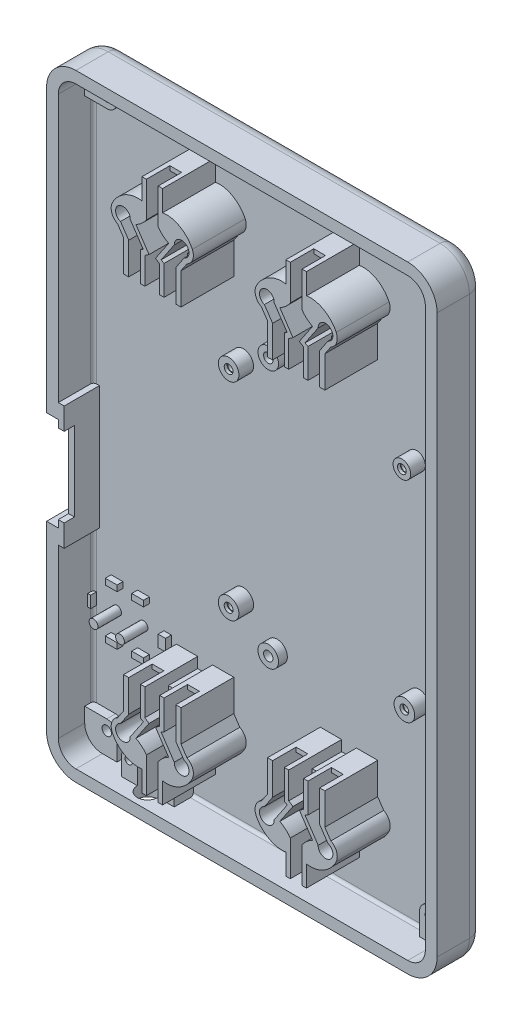
SolidWorks part; units mm, degrees
ref_plane "Alzado" through (0, 0, 0) normal (0, 0, 1) x (1, 0, 0)
ref_plane "Planta" through (0, 0, 0) normal (0, 1, 0) x (1, 0, 0)
ref_plane "Vista lateral" through (0, 0, 0) normal (1, 0, 0) x (0, 0, -1)
sketch "Croquis1" plane through (0, 0, 0) normal (0, 0, 1) x (1, 0, 0)
  line L1 (-97.3166, 96.9231) -> (15.6834, 96.9231)
  line L2 (-107.3166, 86.9231) -> (-107.3166, -103.0769)
  line L3 (-97.3166, -113.0769) -> (15.6834, -113.0769)
  line L4 (25.6834, 86.9231) -> (25.6834, -103.0769)
  arc A0 (15.6834, 96.9231) -> (25.6834, 86.9231) centre (15.6834, 86.9231) cw
  arc A1 (-97.3166, 96.9231) -> (-107.3166, 86.9231) centre (-97.3166, 86.9231) ccw
  arc A2 (15.6834, -113.0769) -> (25.6834, -103.0769) centre (15.6834, -103.0769) ccw
  arc A3 (-107.3166, -103.0769) -> (-97.3166, -113.0769) centre (-97.3166, -103.0769) ccw
  point P6 (25.6834, 96.9231)
  point P9 (-107.3166, 96.9231)
  point P14 (-107.3166, -113.0769)
  dimension "D3" = 10
  dimension "D1" = 210
  dimension "D2" = 133
extrude "Saliente-Extruir1" add sketch "Croquis1" along normal blind 16
fillet "Redondeo1" radius 5 8 edges at (-40.8166, 96.9231, 0) (22.7544, 93.9941, 0) (25.6834, -8.0769, 0) (22.7544, -110.148, 0) (-40.8166, -113.0769, 0) (-104.3877, -110.148, 0) (-107.3166, -8.0769, 0) (-104.3877, 93.9941, 0)
shell "Vaciado1" thickness 4 removed face at (-40.8166, -8.0769, 16)
sketch "Croquis4" plane through (0, 0, 0) normal (0, 0, 1) x (1, 0, 0)
  line L11 (-95.8166, 81.9231) -> (-103.3166, 81.9231)
  line L12 (-97.3166, -109.0769) -> (15.6834, -109.0769) construction
  line L17 (-103.3166, 86.9231) -> (-103.3166, -103.0769) construction
  line L19 (-85.549, -109.0769) -> (-78.3884, -109.0769)
  line L23 (-92.3166, 85.4231) -> (-92.3166, 92.9231)
  line L40 (15.6834, 92.9231) -> (-97.3166, 92.9231) construction
  line L42 (-85.549, -109.0769) -> (-85.549, -113.0769)
  line L43 (-107.3166, -8.0769) -> (25.6834, -8.0769)
  line L44 (-85.549, -113.0769) -> (-78.3884, -113.0769)
  line L45 (-78.3884, -109.0769) -> (-78.3884, -113.0769)
  line L47 (14.1834, 81.9231) -> (21.6834, 81.9231)
  line L48 (25.6834, -113.0769) -> (-107.3166, -113.0769)
  line L50 (25.6834, -113.0769) -> (25.6834, 96.9231)
  line L51 (25.6834, 96.9231) -> (-107.3166, 96.9231)
  line L52 (-107.3166, -113.0769) -> (-107.3166, 96.9231)
  line L53 (10.6834, 85.4231) -> (10.6834, 92.9231)
  line L54 (-92.3166, -101.5769) -> (-92.3166, -109.0769)
  line L55 (-95.8166, -98.0769) -> (-103.3166, -98.0769)
  line L56 (10.6834, -101.5769) -> (10.6834, -109.0769)
  line L57 (14.1834, -98.0769) -> (21.6834, -98.0769)
  circle A6 centre (-95.8166, 85.4231) radius 3.5
  circle A12 centre (-95.8166, 85.4231) radius 1.6
  circle A13 centre (-40.8166, -52.0552) radius 1.6
  circle A14 centre (14.1834, 85.4231) radius 1.6
  circle A15 centre (14.1834, 85.4231) radius 3.5
  circle A16 centre (-40.8166, 35.9013) radius 1.6
  circle A17 centre (-95.8166, -101.5769) radius 1.6
  circle A18 centre (-95.8166, -101.5769) radius 3.5
  circle A19 centre (14.1834, -101.5769) radius 1.6
  circle A20 centre (14.1834, -101.5769) radius 3.5
  arc A21 (-103.3166, 81.9231) -> (-92.3166, 92.9231) centre (-95.8166, 85.4231) cw
  arc A22 (10.6834, 92.9231) -> (21.6834, 81.9231) centre (14.1834, 85.4231) cw
  arc A23 (21.6834, -98.0769) -> (10.6834, -109.0769) centre (14.1834, -101.5769) cw
  arc A24 (-103.3166, -98.0769) -> (-92.3166, -109.0769) centre (-95.8166, -101.5769) ccw
  circle A25 centre (-40.8166, -52.0552) radius 3.5
  circle A26 centre (-40.8166, 35.9013) radius 3.5
extrude "Cortar-Extruir5" cut sketch "Croquis4" along normal through all both and the other way through all from surface contours A17 | A19 | A14 | A12 region at (-95.8166, 85.4231, 0) region at (14.1834, 85.4231, 0) region at (-95.8166, -101.5769, 0) region at (14.1834, -101.5769, 0) starting at face at (-40.8166, -8.0769, 4)
extrude "Cortar-Extruir6" cut sketch "Croquis4<19>" along normal blind 3 from surface contours A6 A12 | A15 A14 | A18 A17 | A20 A19 region at (-98.2215, 87.828, 0) region at (11.7785, 83.0182, 0) region at (-98.2215, -103.9818, 0) region at (11.7785, -99.172, 0) starting at face at (-97.4166, 85.4231, 0)
sketch "Croquis4<19>" plane through (0, 0, 0) normal (0, 0, 1) x (1, 0, 0) same geometry as "Croquis4"
extrude "Saliente-Extruir14" add sketch "Croquis4<21>" along normal blind 3 from surface contours L55 A24 L54 A18 | A18 A17 | A20 A19 | A23 L57 A20 L56 | A22 L53 A15 L47 | A21 L11 A6 L23 | A6 A12 | A15 A14 region at (-98.7646, 88.371, 0) region at (-98.2215, 87.828, 0) region at (17.1313, 88.371, 0) region at (11.7785, 83.0182, 0) region at (-98.2215, -103.9818, 0) region at (-98.7646, -104.5248, 0) region at (17.1313, -104.5248, 0) region at (11.7785, -99.172, 0) starting at face at (-97.4166, 85.4231, 4)
sketch "Croquis4<21>" plane through (0, 0, 0) normal (0, 0, 1) x (1, 0, 0) same geometry as "Croquis4"
extrude "Saliente-Extruir23" add sketch "Croquis4<27>" along normal blind 3 from surface contours A25 A13 | A26 A16 region at (-44.2176, -52.0552, 0) region at (-44.2176, 35.9013, 0) starting at face at (-40.8166, -8.0769, 4)
sketch "Croquis4<27>" plane through (0, 0, 0) normal (0, 0, 1) x (1, 0, 0) same geometry as "Croquis4"
extrude "Cortar-Extruir23" cut sketch "Croquis4<25>" along normal blind 3 from surface contours A26 A16 | A25 region at (-44.2176, 35.9013, 0) starting at face at (10.6834, 85.4231, 0)
sketch "Croquis4<25>" plane through (0, 0, 0) normal (0, 0, 1) x (1, 0, 0) same geometry as "Croquis4"
extrude "Cortar-Extruir22" cut sketch "Croquis4<24>" along normal blind 4 contours A16 | A16 | A13 | A13 region at (-40.8166, -52.0552, 0) region at (-40.8166, 35.9013, 0)
sketch "Croquis4<24>" plane through (0, 0, 0) normal (0, 0, 1) x (1, 0, 0) same geometry as "Croquis4"
sketch "Croquis5" plane through (0, 0, 0) normal (0, 0, 1) x (1, 0, 0)
  line L150 (-10.7322, 67.714) -> (-15.2148, 61.0683)
  line L241 (-107.3158, 96.9231) -> (-100.3166, 96.9231)
  line L242 (-107.3158, 96.9231) -> (-107.3158, 86.9231)
  line L253 (25.6842, -113.0769) -> (-107.3158, -113.0769)
  line L254 (25.6842, -113.0769) -> (25.6842, 96.9231)
  line L255 (25.6842, 96.9231) -> (-107.3158, 96.9231)
  line L257 (-107.3158, -113.0769) -> (-107.3158, 96.9231)
  line L269 (-21.5054, -83.2876) -> (-11.1236, -83.2876)
  line L290 (20.6834, 81.9231) -> (20.6834, -98.0769) construction
  line L298 (20.6834, 41.9231) -> (20.6834, 91.9231)
  line L319 (-6.5409, 51.0127) -> (-6.5409, 61.7386)
  line L321 (-20.3378, 51.0127) -> (-18.8378, 51.0127)
  line L323 (-24.3378, 52.515) -> (-20.3378, 52.515)
  line L325 (-13.7911, 56.1125) -> (-13.7911, 54.6136)
  line L327 (-19.3441, 61.5758) -> (-20.3378, 61.013)
  line L329 (-15.2148, 61.0683) -> (-13.7911, 60.108)
  line L331 (-18.3145, 81.3376) -> (-14.3145, 81.3376)
  line L333 (-12.2911, 61.013) -> (-12.2911, 51.0127)
  line L334 (-13.2849, 61.5758) -> (-12.2911, 61.013)
  line L448 (-22.0816, -81.7882) -> (-23.0929, -83.2876)
  line L529 (-20.3378, 51.0127) -> (-20.3378, 52.515)
  line L533 (-79.3166, -65.3411) -> (-76.8166, -65.3411)
  line L534 (-8.2911, -76.2618) -> (-8.2911, -74.757)
  line L536 (-105.3158, -41.0434) -> (-107.3716, -41.0434)
  line L537 (-24.3378, -67.1665) -> (-24.3378, -68.6689)
  line L538 (-21.8968, -83.8679) -> (-17.4141, -77.2221)
  line L540 (-24.3378, -77.98) -> (-24.3378, -67.1665)
  line L541 (-8.2911, -77.98) -> (-8.2911, -67.1665)
  line L542 (-26.088, -77.8924) -> (-28.1332, -80.9245)
  line L543 (-14.3145, -98.9873) -> (-14.3145, -97.4915)
  line L544 (-20.3378, -74.757) -> (-20.3378, -76.2618)
  line L545 (-20.3378, -77.1668) -> (-20.3378, -67.1665)
  line L546 (-12.8145, -98.9873) -> (-12.8145, -91.832)
  line L547 (-23.8176, -84.362) -> (-19.3441, -77.7297)
  line L548 (-18.8378, -72.2663) -> (-18.8378, -70.7675)
  line L551 (-8.2911, -67.1665) -> (-8.2911, -68.6689)
  line L552 (-8.2911, -77.98) -> (-5.4952, -82.1252)
  line L553 (-18.8378, -70.7675) -> (-13.7911, -70.7675)
  line L554 (-12.2911, -74.757) -> (-8.2911, -74.757)
  line L555 (-12.2911, -67.1665) -> (-8.2911, -67.1665)
  line L557 (-6.5409, -77.8924) -> (-4.4957, -80.9245)
  line L562 (20.6834, 81.9231) -> (20.6834, -98.0769) construction
  line L563 (-102.3166, -98.0769) -> (-102.3166, 81.9231) construction
  line L564 (-14.3145, -98.9873) -> (-14.3145, -86.9871)
  line L565 (-10.5473, -81.7882) -> (-5.7225, -81.7882)
  line L616 (-23.0929, -83.2876) -> (-28.5079, -83.2876)
  line L617 (-20.3378, -74.757) -> (-24.3378, -74.757)
  line L635 (-24.3378, -67.1665) -> (-26.088, -67.1665)
  line L650 (-18.3145, -86.9871) -> (-18.3145, -98.9873)
  line L652 (-12.2911, -67.1665) -> (-12.2911, -68.6689)
  line L653 (-24.3378, -67.1665) -> (-20.3378, -67.1665)
  line L661 (-18.3145, -98.9873) -> (-14.3145, -98.9873)
  line L662 (-18.3145, -98.9873) -> (-19.8145, -98.9873)
  line L665 (-13.7911, -76.2618) -> (-13.7911, -67.1665)
  line L666 (-9.536, -83.2876) -> (-4.121, -83.2876)
  line L667 (-12.2911, -68.6689) -> (-8.2911, -68.6689)
  line L668 (-18.3145, -98.9873) -> (-18.3145, -86.9871)
  line L669 (-20.494, -81.7882) -> (-12.1349, -81.7882)
  line L671 (-12.2911, -76.2618) -> (-8.2911, -76.2618)
  line L673 (-12.2911, -67.1665) -> (-13.7911, -67.1665)
  line L674 (-19.8145, -98.9873) -> (-19.8145, -91.832)
  line L675 (-24.3378, -74.757) -> (-24.3378, -76.2618)
  line L676 (-12.2911, -76.2618) -> (-12.2911, -74.757)
  line L677 (-17.4141, -77.2221) -> (-18.8378, -76.2618)
  line L679 (-79.3166, -65.3411) -> (-79.3166, -69.3411)
  line L681 (-26.9065, -81.7882) -> (-22.0816, -81.7882)
  line L682 (-8.2911, -67.1665) -> (-6.5409, -67.1665)
  line L683 (-24.3378, -77.98) -> (-27.1338, -82.1252)
  line L684 (-14.3145, -86.9871) -> (-14.3145, -98.9873)
  line L685 (-18.8378, -76.2618) -> (-18.8378, -67.1665)
  line L687 (-14.3145, -98.9873) -> (-12.8145, -98.9873)
  line L689 (-18.8378, -72.2663) -> (-13.7911, -72.2663)
  line L690 (-97.3166, -109.0769) -> (15.6834, -109.0769) construction
  line L691 (-81.878, -113.0769) -> (-74.9407, -113.0769)
  line L692 (-81.878, -113.0769) -> (-81.878, -109.0769)
  line L693 (-81.878, -109.0769) -> (-74.9407, -109.0769)
  line L694 (-74.9407, -113.0769) -> (-74.9407, -109.0769)
  line L695 (-87.3438, -109.0769) -> (-81.878, -109.0769)
  line L697 (-84.8438, -103.0769) -> (-71.844, -103.0769)
  line L698 (-87.3438, -103.0769) -> (-87.3438, -109.0769)
  line L699 (-84.8438, -100.5769) -> (-71.844, -100.5769)
  line L700 (-69.344, -103.0769) -> (-69.344, -109.0769)
  line L701 (-92.3166, -109.0769) -> (10.6834, -109.0769) construction
  line L702 (-74.9407, -109.0769) -> (-69.344, -109.0769)
  line L704 (-78.4093, -109.0769) -> (-78.4093, -113.0769)
  line L705 (-102.3166, -74.8411) -> (-79.3166, -74.8411)
  line L706 (-102.3166, -74.8411) -> (-102.3166, -59.8411)
  line L707 (-102.3166, -59.8411) -> (-79.3166, -59.8411)
  line L708 (-79.3166, -74.8411) -> (-79.3166, -59.8411)
  line L709 (-79.3166, -74.8411) -> (-84.3166, -74.8411)
  line L710 (-79.3166, -74.8411) -> (-79.3166, -59.8411)
  line L711 (-79.3166, -59.8411) -> (-84.3166, -59.8411)
  line L713 (-97.3166, -59.8411) -> (-93.3166, -59.8411)
  line L714 (-93.3166, -59.8411) -> (-88.3166, -59.8411)
  line L716 (-93.3166, -74.8411) -> (-88.3166, -74.8411)
  line L718 (-97.3166, -59.8411) -> (-97.3166, -74.8411)
  line L719 (-97.3166, -74.8411) -> (-93.3166, -74.8411)
  line L720 (-93.3166, -59.8411) -> (-93.3166, -74.8411)
  line L722 (-102.3166, -59.8411) -> (-97.3166, -59.8411)
  line L723 (-102.3166, -59.8411) -> (-102.3166, -74.8411)
  line L724 (-102.3166, -74.8411) -> (-97.3166, -74.8411)
  line L726 (-88.3166, -59.8411) -> (-84.3166, -59.8411)
  line L727 (-88.3166, -59.8411) -> (-88.3166, -74.8411)
  line L728 (-88.3166, -74.8411) -> (-84.3166, -74.8411)
  line L729 (-84.3166, -59.8411) -> (-84.3166, -74.8411)
  line L730 (-102.3166, -59.8411) -> (-79.3166, -59.8411)
  line L734 (-79.3166, -74.8411) -> (-102.3166, -74.8411)
  line L738 (-79.3166, -69.3411) -> (-76.8166, -69.3411)
  line L743 (-102.3166, -65.3411) -> (-102.3166, -69.3411)
  line L744 (-76.8166, -65.3411) -> (-76.8166, -69.3411)
  line L745 (-8.8113, -84.362) -> (-13.2849, -77.7297)
  line L746 (-26.088, -67.1665) -> (-26.088, -77.8924)
  line L751 (-79.3166, -69.3411) -> (-79.3166, -65.3411)
  line L754 (-79.3166, -65.3411) -> (-79.3166, -69.3411)
  line L757 (-97.3166, -74.8411) -> (-93.3166, -74.8411)
  line L758 (-97.3166, -74.8411) -> (-97.3166, -76.8411)
  line L759 (-97.3166, -76.8411) -> (-93.3166, -76.8411)
  line L760 (-93.3166, -74.8411) -> (-93.3166, -76.8411)
  line L761 (-88.3166, -74.8411) -> (-84.3166, -74.8411)
  line L762 (-88.3166, -74.8411) -> (-88.3166, -76.8411)
  line L763 (-88.3166, -76.8411) -> (-84.3166, -76.8411)
  line L764 (-84.3166, -74.8411) -> (-84.3166, -76.8411)
  line L765 (-97.3166, -59.8411) -> (-93.3166, -59.8411)
  line L766 (-97.3166, -59.8411) -> (-97.3166, -57.8411)
  line L767 (-97.3166, -57.8411) -> (-93.3166, -57.8411)
  line L768 (-93.3166, -59.8411) -> (-93.3166, -57.8411)
  line L769 (-88.3166, -59.8411) -> (-84.3166, -59.8411)
  line L770 (-88.3166, -59.8411) -> (-88.3166, -57.8411)
  line L771 (-88.3166, -57.8411) -> (-84.3166, -57.8411)
  line L772 (-84.3166, -59.8411) -> (-84.3166, -57.8411)
  line L776 (-103.3166, 81.9231) -> (-103.3166, -98.0769) construction
  line L777 (-107.3158, -41.0434) -> (-77.3158, -41.0434)
  line L778 (-107.3158, -41.0434) -> (-107.3158, -9.0434)
  line L779 (-107.3158, -9.0434) -> (-77.3158, -9.0434)
  line L780 (-77.3158, -41.0434) -> (-77.3158, -9.0434)
  line L781 (-77.3158, -41.0434) -> (-87.3158, -41.0434)
  line L782 (-77.3158, -41.0434) -> (-77.3158, -9.0434)
  line L783 (-77.3158, -9.0434) -> (-87.3158, -9.0434)
  line L784 (-87.3158, -41.0434) -> (-87.3158, -9.0434)
  line L785 (-107.3158, -9.0434) -> (-87.3158, -9.0434)
  line L786 (-107.3158, -9.0434) -> (-107.3158, -13.0467)
  line L787 (-107.3158, -13.0467) -> (-87.3158, -13.0467)
  line L788 (-87.3158, -9.0434) -> (-87.3158, -13.0467)
  line L789 (-87.3158, -13.0467) -> (-77.3158, -13.0467)
  line L790 (-87.3158, -13.0467) -> (-87.3158, -27.5467)
  line L791 (-87.3158, -27.5467) -> (-77.3158, -27.5467)
  line L792 (-77.3158, -13.0467) -> (-77.3158, -27.5467)
  line L793 (-87.3158, -41.0434) -> (-105.3158, -41.0434)
  line L794 (-87.3158, -41.0434) -> (-87.3158, -9.0434)
  line L795 (-87.3158, -9.0434) -> (-105.3158, -9.0434)
  line L796 (-105.3158, -41.0434) -> (-105.3158, -9.0434)
  line L797 (-105.3158, -9.0434) -> (-103.3166, -9.0434)
  line L798 (-105.3158, -9.0434) -> (-105.3158, -41.0434)
  line L799 (-105.3158, -41.0434) -> (-103.3166, -41.0434)
  line L800 (-103.3166, -9.0434) -> (-103.3166, -41.0434)
  line L801 (-105.3158, -41.0434) -> (-105.3158, -13.0467)
  line L802 (-103.3166, -9.0434) -> (-101.3158, -9.0434)
  line L803 (-103.3166, -9.0434) -> (-103.3166, -11.5434)
  line L804 (-103.3166, -11.5434) -> (-101.3158, -11.5434)
  line L805 (-101.3158, -9.0434) -> (-101.3158, -11.5434)
  line L806 (-103.3166, -41.0434) -> (-101.3158, -41.0434)
  line L807 (-103.3166, -41.0434) -> (-103.3166, -38.5434)
  line L808 (-103.3166, -38.5434) -> (-101.3158, -38.5434)
  line L809 (-101.3158, -41.0434) -> (-101.3158, -38.5434)
  line L810 (-101.3158, -9.0434) -> (-103.3166, -9.0434)
  line L811 (-101.3158, -9.0434) -> (-101.3158, -4.0434)
  line L812 (-101.3158, -4.0434) -> (-103.3166, -4.0434)
  line L813 (-103.3166, -9.0434) -> (-103.3166, -4.0434)
  line L814 (-101.3158, -41.0434) -> (-103.3166, -41.0434)
  line L815 (-101.3158, -41.0434) -> (-101.3158, -46.0434)
  line L816 (-101.3158, -46.0434) -> (-103.3166, -46.0434)
  line L817 (-103.3166, -41.0434) -> (-103.3166, -46.0434)
  line L818 (-101.3158, -11.5434) -> (-103.3166, -11.5434)
  line L819 (-101.3158, -11.5434) -> (-101.3158, -38.5434)
  line L820 (-101.3158, -38.5434) -> (-103.3166, -38.5434)
  line L821 (-103.3166, -11.5434) -> (-103.3166, -38.5434)
  line L822 (-56.3166, 31.4433) -> (10.6834, 31.4433)
  line L823 (-56.3166, 31.4433) -> (-56.3166, -46.5567)
  line L824 (-56.3166, -46.5567) -> (10.6834, -46.5567)
  line L825 (10.6834, 31.4433) -> (10.6834, -46.5567)
  line L826 (-20.3378, 60.108) -> (-24.3378, 60.108)
  line L827 (-18.3145, 82.8335) -> (-18.3145, 81.3376)
  line L828 (-56.3166, 31.4433) -> (-50.5567, 31.4433)
  line L829 (10.6834, 31.4433) -> (5.0745, 31.4433)
  line L830 (10.6834, 31.4433) -> (10.6834, 28.1628)
  line L833 (10.6834, -46.5567) -> (4.7834, -46.5567)
  line L834 (10.6834, -46.5567) -> (10.6834, -43.3567)
  line L837 (-56.3166, 31.4433) -> (-56.3166, 27.9366)
  line L840 (-56.3166, -46.5567) -> (-50.394, -46.5567)
  line L841 (-56.3166, -46.5567) -> (-56.3166, -42.7216)
  line L846 (-18.3145, -98.9873) -> (-18.3145, -97.4915)
  line L847 (-20.3378, -76.2618) -> (-24.3378, -76.2618)
  line L848 (-20.3378, -67.1665) -> (-20.3378, -68.6689)
  line L849 (-13.2849, -77.7297) -> (-12.2911, -77.1668)
  line L850 (-12.2911, -77.1668) -> (-12.2911, -67.1665)
  line L851 (-18.3145, -97.4915) -> (-14.3145, -97.4915)
  line L853 (-15.2148, -77.2221) -> (-13.7911, -76.2618)
  line L854 (-19.3441, -77.7297) -> (-20.3378, -77.1668)
  line L857 (-13.7911, -72.2663) -> (-13.7911, -70.7675)
  line L858 (-24.3378, -68.6689) -> (-20.3378, -68.6689)
  line L859 (-20.3378, -67.1665) -> (-18.8378, -67.1665)
  line L862 (-6.5409, -67.1665) -> (-6.5409, -77.8924)
  line L865 (-10.7322, -83.8679) -> (-15.2148, -77.2221)
  line L866 (-26.088, 51.0127) -> (-26.088, 61.7386)
  line L867 (-8.8113, 68.2081) -> (-13.2849, 61.5758)
  line L868 (-18.8378, 56.1125) -> (-13.7911, 56.1125)
  line L869 (-14.3145, 82.8335) -> (-12.8145, 82.8335)
  line L870 (-18.8378, 60.108) -> (-18.8378, 51.0127)
  line L871 (-14.3145, 70.8333) -> (-14.3145, 82.8335)
  line L873 (-24.3378, 61.8262) -> (-27.1338, 65.9714)
  line L874 (-8.2911, 51.0127) -> (-6.5409, 51.0127)
  line L876 (-26.9065, 65.6344) -> (-22.0816, 65.6344)
  line L877 (-17.4141, 61.0683) -> (-18.8378, 60.108)
  line L878 (-12.2911, 60.108) -> (-12.2911, 58.6032)
  line L881 (-24.3378, 58.6032) -> (-24.3378, 60.108)
  line L882 (-19.8145, 82.8335) -> (-19.8145, 75.6781)
  line L884 (-12.2911, 51.0127) -> (-13.7911, 51.0127)
  line L885 (-12.2911, 60.108) -> (-8.2911, 60.108)
  line L887 (-20.494, 65.6344) -> (-12.1349, 65.6344)
  line L888 (-18.3145, 82.8335) -> (-18.3145, 70.8333)
  line L889 (-12.2911, 52.515) -> (-8.2911, 52.515)
  line L891 (-9.536, 67.1338) -> (-4.121, 67.1338)
  line L892 (-13.7911, 60.108) -> (-13.7911, 51.0127)
  line L893 (-18.3145, 82.8335) -> (-19.8145, 82.8335)
  line L895 (-18.3145, 82.8335) -> (-14.3145, 82.8335)
  line L896 (-24.3378, 51.0127) -> (-20.3378, 51.0127)
  line L897 (-12.2911, 51.0127) -> (-12.2911, 52.515)
  line L899 (-18.3145, 70.8333) -> (-18.3145, 82.8335)
  line L900 (-24.3378, 51.0127) -> (-26.088, 51.0127)
  line L901 (-20.3378, 58.6032) -> (-24.3378, 58.6032)
  line L903 (-23.0929, 67.1338) -> (-28.5079, 67.1338)
  line L904 (-10.5473, 65.6344) -> (-5.7225, 65.6344)
  line L905 (-14.3145, 82.8335) -> (-14.3145, 70.8333)
  line L906 (-6.5409, 61.7386) -> (-4.4957, 64.7707)
  line L907 (-12.2911, 51.0127) -> (-8.2911, 51.0127)
  line L910 (-12.2911, 58.6032) -> (-8.2911, 58.6032)
  line L911 (-18.8378, 54.6136) -> (-13.7911, 54.6136)
  line L913 (-8.2911, 61.8262) -> (-5.4952, 65.9714)
  line L914 (-8.2911, 51.0127) -> (-8.2911, 52.515)
  line L916 (-18.8378, 56.1125) -> (-18.8378, 54.6136)
  line L917 (-23.8176, 68.2081) -> (-19.3441, 61.5758)
  line L918 (-12.8145, 82.8335) -> (-12.8145, 75.6781)
  line L919 (-20.3378, 61.013) -> (-20.3378, 51.0127)
  line L920 (-20.3378, 58.6032) -> (-20.3378, 60.108)
  line L921 (-14.3145, 82.8335) -> (-14.3145, 81.3376)
  line L923 (-26.088, 61.7386) -> (-28.1332, 64.7707)
  line L924 (-8.2911, 61.8262) -> (-8.2911, 51.0127)
  line L925 (-24.3378, 61.8262) -> (-24.3378, 51.0127)
  line L927 (-21.8968, 67.714) -> (-17.4141, 61.0683)
  line L928 (-24.3378, 51.0127) -> (-24.3378, 52.515)
  line L929 (-8.2911, 60.108) -> (-8.2911, 58.6032)
  line L930 (-22.0816, 65.6344) -> (-23.0929, 67.1338)
  line L934 (-21.5054, 67.1338) -> (-11.1236, 67.1338)
  line L937 (-105.3158, -13.0467) -> (-107.3716, -13.0467)
  line L938 (-60.1262, 67.1338) -> (-70.508, 67.1338)
  line L939 (-59.55, 65.6344) -> (-58.5386, 67.1338)
  line L941 (-73.3404, 60.108) -> (-73.3404, 58.6032)
  line L942 (-57.2938, 51.0127) -> (-57.2938, 52.515)
  line L943 (-59.7348, 67.714) -> (-64.2174, 61.0683)
  line L944 (-57.2938, 61.8262) -> (-57.2938, 51.0127)
  line L945 (-73.3404, 61.8262) -> (-73.3404, 51.0127)
  line L946 (-55.5435, 61.7386) -> (-53.4983, 64.7707)
  line L947 (-67.3171, 82.8335) -> (-67.3171, 81.3376)
  line L949 (-61.2938, 58.6032) -> (-61.2938, 60.108)
  line L950 (-61.2938, 61.013) -> (-61.2938, 51.0127)
  line L951 (-68.8171, 82.8335) -> (-68.8171, 75.6781)
  line L952 (-57.814, 68.2081) -> (-62.2875, 61.5758)
  line L953 (-62.7938, 56.1125) -> (-62.7938, 54.6136)
  line L955 (-73.3404, 51.0127) -> (-73.3404, 52.515)
  line L956 (-73.3404, 61.8262) -> (-76.1364, 65.9714)
  line L957 (-62.7938, 54.6136) -> (-67.8404, 54.6136)
  line L959 (-69.3404, 58.6032) -> (-73.3404, 58.6032)
  line L960 (-69.3404, 51.0127) -> (-73.3404, 51.0127)
  line L961 (-75.0906, 61.7386) -> (-77.1358, 64.7707)
  line L962 (-67.3171, 82.8335) -> (-67.3171, 70.8333)
  line L963 (-71.0842, 65.6344) -> (-75.9091, 65.6344)
  line L964 (-58.5386, 67.1338) -> (-53.1237, 67.1338)
  line L966 (-61.2938, 58.6032) -> (-57.2938, 58.6032)
  line L967 (-57.2938, 51.0127) -> (-55.5435, 51.0127)
  line L968 (-63.3171, 70.8333) -> (-63.3171, 82.8335)
  line L969 (-69.3404, 51.0127) -> (-69.3404, 52.515)
  line L970 (-62.7925, -72.2582) -> (-62.7925, -70.7594)
  line L971 (-67.8391, -70.7594) -> (-62.7925, -70.7594)
  line L972 (-67.8391, -72.2582) -> (-67.8391, -70.7594)
  line L973 (-67.8391, -72.2582) -> (-62.7925, -72.2582)
  line L974 (-63.3158, -98.9792) -> (-63.3158, -97.4834)
  line L975 (-67.3158, -97.4834) -> (-63.3158, -97.4834)
  line L976 (-67.3158, -98.9792) -> (-67.3158, -97.4834)
  line L977 (-67.3158, -98.9792) -> (-63.3158, -98.9792)
  line L978 (-59.5486, -81.7801) -> (-54.7238, -81.7801)
  line L979 (-69.4953, -81.7801) -> (-61.1362, -81.7801)
  line L980 (-58.5373, -83.2795) -> (-53.1224, -83.2795)
  line L981 (-70.5067, -83.2795) -> (-60.1249, -83.2795)
  line L982 (-72.0942, -83.2795) -> (-77.5092, -83.2795)
  line L983 (-71.0829, -81.7801) -> (-72.0942, -83.2795)
  line L984 (-73.3391, -74.7489) -> (-73.3391, -76.2537)
  line L985 (-69.3391, -76.2537) -> (-73.3391, -76.2537)
  line L986 (-69.3391, -74.7489) -> (-69.3391, -76.2537)
  line L987 (-69.3391, -74.7489) -> (-73.3391, -74.7489)
  line L988 (-57.2925, -76.2537) -> (-57.2925, -74.7489)
  line L989 (-61.2925, -74.7489) -> (-57.2925, -74.7489)
  line L990 (-61.2925, -76.2537) -> (-61.2925, -74.7489)
  line L991 (-61.2925, -76.2537) -> (-57.2925, -76.2537)
  line L992 (-57.2925, -67.1584) -> (-57.2925, -68.6608)
  line L993 (-61.2925, -68.6608) -> (-57.2925, -68.6608)
  line L994 (-61.2925, -67.1584) -> (-61.2925, -68.6608)
  line L995 (-61.2925, -67.1584) -> (-57.2925, -67.1584)
  line L996 (-69.3391, -67.1584) -> (-69.3391, -68.6608)
  line L997 (-73.3391, -68.6608) -> (-69.3391, -68.6608)
  line L998 (-73.3391, -67.1584) -> (-73.3391, -68.6608)
  line L999 (-73.3391, -67.1584) -> (-69.3391, -67.1584)
  line L1000 (-69.3391, -77.1587) -> (-69.3391, -67.1584)
  line L1001 (-67.3158, -98.9792) -> (-68.8158, -98.9792)
  line L1002 (-62.7925, -76.2537) -> (-62.7925, -67.1584)
  line L1003 (-57.2925, -67.1584) -> (-55.5422, -67.1584)
  line L1004 (-73.3391, -77.9719) -> (-76.1351, -82.1171)
  line L1005 (-62.2862, -77.7216) -> (-61.2925, -77.1587)
  line L1006 (-64.2161, -77.214) -> (-62.7925, -76.2537)
  line L1007 (-61.2925, -67.1584) -> (-62.7925, -67.1584)
  line L1008 (-73.3391, -77.9719) -> (-73.3391, -67.1584)
  line L1009 (-63.3158, -86.979) -> (-63.3158, -98.9792)
  line L1010 (-57.8126, -84.3539) -> (-62.2862, -77.7216)
  line L1011 (-69.3391, -67.1584) -> (-67.8391, -67.1584)
  line L1012 (-67.8391, -76.2537) -> (-67.8391, -67.1584)
  line L1013 (-57.2925, -77.9719) -> (-57.2925, -67.1584)
  line L1014 (-55.5422, -77.8843) -> (-53.497, -80.9164)
  line L1015 (-73.3391, -67.1584) -> (-75.0893, -67.1584)
  line L1016 (-55.5422, -67.1584) -> (-55.5422, -77.8843)
  line L1017 (-68.8158, -98.9792) -> (-68.8158, -91.8239)
  line L1018 (-66.4154, -77.214) -> (-67.8391, -76.2537)
  line L1019 (-68.3454, -77.7216) -> (-69.3391, -77.1587)
  line L1020 (-61.8158, -98.9792) -> (-61.8158, -91.8239)
  line L1021 (-67.3158, -98.9792) -> (-67.3158, -86.979)
  line L1022 (-75.0893, -67.1584) -> (-75.0893, -77.8843)
  line L1023 (-75.0893, -77.8843) -> (-77.1345, -80.9164)
  line L1024 (-57.2925, -77.9719) -> (-54.4965, -82.1171)
  line L1025 (-59.7335, -83.8597) -> (-64.2161, -77.214)
  line L1026 (-70.8981, -83.8597) -> (-66.4154, -77.214)
  line L1027 (-63.3158, -98.9792) -> (-63.3158, -86.979)
  line L1028 (-61.2925, -77.1587) -> (-61.2925, -67.1584)
  line L1029 (-63.3158, -98.9792) -> (-61.8158, -98.9792)
  line L1030 (-72.8189, -84.3539) -> (-68.3454, -77.7216)
  line L1031 (-67.3158, -86.979) -> (-67.3158, -98.9792)
  line L1032 (-75.9078, -81.7801) -> (-71.0829, -81.7801)
  line L1033 (-57.2938, 51.0127) -> (-61.2938, 51.0127)
  line L1034 (-102.3166, -69.3411) -> (-103.3166, -69.3411)
  line L1035 (-102.3166, -69.3411) -> (-102.3166, -65.3411)
  line L1036 (-102.3166, -65.3411) -> (-103.3166, -65.3411)
  line L1037 (-103.3166, -69.3411) -> (-103.3166, -65.3411)
  line L1038 (-63.3171, 82.8335) -> (-67.3171, 82.8335)
  line L1039 (-63.3171, 82.8335) -> (-61.8171, 82.8335)
  line L1040 (-67.8404, 60.108) -> (-67.8404, 51.0127)
  line L1041 (-72.0956, 67.1338) -> (-77.5105, 67.1338)
  line L1042 (-69.3404, 52.515) -> (-73.3404, 52.515)
  line L1043 (-63.3171, 82.8335) -> (-63.3171, 70.8333)
  line L1044 (-61.1375, 65.6344) -> (-69.4967, 65.6344)
  line L1045 (-69.3404, 60.108) -> (-73.3404, 60.108)
  line L1046 (-69.3404, 51.0127) -> (-67.8404, 51.0127)
  line L1047 (-61.8171, 82.8335) -> (-61.8171, 75.6781)
  line L1048 (-57.2938, 58.6032) -> (-57.2938, 60.108)
  line L1049 (-69.3404, 60.108) -> (-69.3404, 58.6032)
  line L1050 (-64.2174, 61.0683) -> (-62.7938, 60.108)
  line L1051 (-54.7251, 65.6344) -> (-59.55, 65.6344)
  line L1052 (-73.3404, 51.0127) -> (-75.0906, 51.0127)
  line L1053 (-57.2938, 61.8262) -> (-54.4978, 65.9714)
  line L1054 (-67.3171, 70.8333) -> (-67.3171, 82.8335)
  line L1055 (-62.7938, 60.108) -> (-62.7938, 51.0127)
  line L1056 (-67.3171, 82.8335) -> (-68.8171, 82.8335)
  line L1057 (-62.7938, 56.1125) -> (-67.8404, 56.1125)
  line L1058 (-72.8202, 68.2081) -> (-68.3467, 61.5758)
  line L1059 (-55.5435, 51.0127) -> (-55.5435, 61.7386)
  line L1060 (-63.3171, 82.8335) -> (-63.3171, 81.3376)
  line L1061 (-61.2938, 60.108) -> (-57.2938, 60.108)
  line L1062 (-61.2938, 51.0127) -> (-61.2938, 52.515)
  line L1063 (-68.3467, 61.5758) -> (-69.3404, 61.013)
  line L1064 (-69.3404, 61.013) -> (-69.3404, 51.0127)
  line L1065 (-63.3171, 81.3376) -> (-67.3171, 81.3376)
  line L1066 (-66.4168, 61.0683) -> (-67.8404, 60.108)
  line L1067 (-62.2875, 61.5758) -> (-61.2938, 61.013)
  line L1068 (-67.8404, 56.1125) -> (-67.8404, 54.6136)
  line L1069 (-57.2938, 52.515) -> (-61.2938, 52.515)
  line L1070 (-61.2938, 51.0127) -> (-62.7938, 51.0127)
  line L1071 (-75.0906, 51.0127) -> (-75.0906, 61.7386)
  line L1072 (-70.8994, 67.714) -> (-66.4168, 61.0683)
  line L1073 (-107.3716, -41.0434) -> (-107.3716, -13.0467)
  line L1074 (-105.3158, -13.0467) -> (-107.3716, -13.0467)
  line L1075 (-105.3158, -13.0467) -> (-105.3158, -9.0434)
  line L1076 (-105.3158, -9.0434) -> (-107.3716, -9.0434)
  line L1077 (-107.3716, -13.0467) -> (-107.3716, -9.0434)
  arc A25 (-8.8113, 68.2081) -> (-5.4952, 65.9714) centre (-6.3145, 68.3333) cw
  arc A26 (-2.6705, 69.9831) -> (-4.4957, 64.7707) centre (-6.3145, 68.3333) cw
  arc A28 (-23.8176, 68.2081) -> (-27.1338, 65.9714) centre (-26.3145, 68.3333) ccw
  arc A29 (-29.9584, 69.9831) -> (-28.1332, 64.7707) centre (-26.3145, 68.3333) ccw
  arc A31 (-29.9584, -86.1369) -> (-28.1332, -80.9245) centre (-26.3145, -84.4871) cw
  arc A32 (-23.8176, -84.362) -> (-27.1338, -82.1252) centre (-26.3145, -84.4871) cw
  arc A42 (-2.6705, -86.1369) -> (-4.4957, -80.9245) centre (-6.3145, -84.4871) ccw
  arc A43 (-8.8113, -84.362) -> (-5.4952, -82.1252) centre (-6.3145, -84.4871) ccw
  circle A52 centre (-84.8438, -103.0769) radius 2.5
  circle A53 centre (-71.844, -103.0769) radius 2.5
  circle A54 centre (-84.8438, -103.0769) radius 1.25
  circle A55 centre (-71.844, -103.0769) radius 1.25
  circle A58 centre (6.6834, 27.8433) radius 1.25
  circle A59 centre (6.6834, 27.8433) radius 3
  circle A60 centre (7.5334, -42.6567) radius 1.25
  circle A61 centre (7.5334, -42.6567) radius 3.5
  circle A62 centre (-52.3166, 27.8433) radius 1.25
  circle A63 centre (-52.3166, 27.8433) radius 3.5
  circle A64 centre (-52.3166, -42.5567) radius 3.5
  circle A65 centre (-52.3166, -42.5567) radius 1.25
  circle A67 centre (-52.3166, -42.5567) radius 1.5
  circle A68 centre (7.5334, -42.6567) radius 1.5
  circle A69 centre (6.6834, 27.8433) radius 1.5
  circle A70 centre (-52.3166, 27.8433) radius 1.5
  arc A71 (-51.6732, 69.9831) -> (-53.4983, 64.7707) centre (-55.3171, 68.3333) cw
  arc A72 (-57.814, 68.2081) -> (-54.4978, 65.9714) centre (-55.3171, 68.3333) cw
  arc A73 (-78.961, 69.9831) -> (-77.1358, 64.7707) centre (-75.3171, 68.3333) ccw
  arc A74 (-72.8202, 68.2081) -> (-76.1364, 65.9714) centre (-75.3171, 68.3333) ccw
  arc A79 (-78.9597, -86.1288) -> (-77.1345, -80.9164) centre (-75.3158, -84.479) cw
  arc A80 (-72.8189, -84.3539) -> (-76.1351, -82.1171) centre (-75.3158, -84.479) cw
  arc A81 (-57.8126, -84.3539) -> (-54.4965, -82.1171) centre (-55.3158, -84.479) ccw
  arc A82 (-51.6718, -86.1288) -> (-53.497, -80.9164) centre (-55.3158, -84.479) ccw
  circle A83 centre (-95.3166, -67.3411) radius 1.5
  circle A84 centre (-86.3166, -67.3411) radius 1.5
  spline S4 degree 2 poles (-14.3145, 70.8333) (-12.9373, 68.8195) (-10.7322, 67.714) knots 0 0 0 1 1 1
  spline S5 degree 3 poles (-19.8145, 75.6781) (-23.9864, 76.4463) (-28.2222, 73.6763) (-29.9584, 69.9831) knots 0 0 0 0 1 1 1 1
  spline S6 degree 3 poles (-12.8145, 75.6781) (-8.6425, 76.4463) (-4.4067, 73.6763) (-2.6705, 69.9831) knots 0 0 0 0 1 1 1 1
  spline S7 degree 2 poles (-18.3145, 70.8333) (-19.6916, 68.8195) (-21.8968, 67.714) knots 0 0 0 1 1 1
  spline S8 degree 2 poles (-18.3145, -86.9871) (-19.6916, -84.9733) (-21.8968, -83.8679) knots 0 0 0 1 1 1
  spline S9 degree 3 poles (-12.8145, -91.832) (-8.6425, -92.6001) (-4.4067, -89.8302) (-2.6705, -86.1369) knots 0 0 0 0 1 1 1 1
  spline S10 degree 3 poles (-19.8145, -91.832) (-23.9864, -92.6001) (-28.2222, -89.8302) (-29.9584, -86.1369) knots 0 0 0 0 1 1 1 1
  spline S11 degree 2 poles (-14.3145, -86.9871) (-12.9373, -84.9733) (-10.7322, -83.8679) knots 0 0 0 1 1 1
  spline S12 degree 2 poles (-63.3171, 70.8333) (-61.94, 68.8195) (-59.7348, 67.714) knots 0 0 0 1 1 1
  spline S13 degree 3 poles (-68.8171, 75.6781) (-72.9891, 76.4463) (-77.2248, 73.6763) (-78.961, 69.9831) knots 0 0 0 0 1 1 1 1
  spline S14 degree 3 poles (-61.8171, 75.6781) (-57.6451, 76.4463) (-53.4093, 73.6763) (-51.6732, 69.9831) knots 0 0 0 0 1 1 1 1
  spline S15 degree 2 poles (-67.3171, 70.8333) (-68.6942, 68.8195) (-70.8994, 67.714) knots 0 0 0 1 1 1
  spline S16 degree 2 poles (-63.3158, -86.979) (-61.9386, -84.9652) (-59.7335, -83.8597) knots 0 0 0 1 1 1
  spline S17 degree 2 poles (-67.3158, -86.979) (-68.6929, -84.9652) (-70.8981, -83.8597) knots 0 0 0 1 1 1
  spline S18 degree 3 poles (-68.8158, -91.8239) (-72.9878, -92.592) (-77.2235, -89.822) (-78.9597, -86.1288) knots 0 0 0 0 1 1 1 1
  spline S19 degree 3 poles (-61.8158, -91.8239) (-57.6438, -92.592) (-53.408, -89.822) (-51.6718, -86.1288) knots 0 0 0 0 1 1 1 1
  point P284 (-23.6658, -8.5453)
  dimension "D36" = 6
  dimension "D37" = 32
  dimension "D41" = 4
  dimension "D57" = 4
  dimension "D59" = 4
  dimension "D61" = 4
  dimension "D60" = 3.6
  dimension "D38" = 2.5
  dimension "D39" = 30
  dimension "D40" = 32
  dimension "D43" = 10
  dimension "D44" = 14.5
  dimension "D45" = 18
  dimension "D46" = 2.5
  dimension "D47" = 2.5
  dimension "D48" = 5
  dimension "D49" = 5
  dimension "D50" = 32.3751
  dimension "D51" = 28.9065
  dimension "D52" = 67
  dimension "D53" = 78
  dimension "D54" = 10
  dimension "D55" = 3.9
  dimension "D56" = 4
  dimension "D58" = 3.15
  dimension "3.6" = 3.6
  dimension "D86" = 5
  dimension "D87" = 5
  dimension "D88" = 5
  dimension "D89" = 4
extrude "Guia contactos" add sketch "Croquis5" along normal blind 18 from surface contours A25 L869 L866 L826 | L529 | S15 L962 L947 L1056 L951 S13 A73 L961 L1071 L1052 L945 L941 L956 A74 L1058 L1063 L1064 L1049 L969 L1046 L1040 L1066 L1072 | S14 L1047 L1039 L1043 L968 S12 L943 L1050 L1055 L953 L1070 L950 L949 L1067 L952 L939 A72 L1053 L944 L942 L967 L1059 L946 A71 | S18 L1017 L1001 L976 L1021 S17 L1026 L1018 L1012 L972 L1011 L996 L1000 L986 L1019 L1030 L983 A80 L1004 L1008 L984 L998 L1015 L1022 L1023 A79 | L1020 S19 A82 L1014 L1016 L1003 L992 L1013 L988 L1024 A81 L1010 L1005 L1028 L990 L994 L1007 L1002 L970 L1006 L1025 S16 L1009 L974 L1029 | S10 L674 L662 L668 L650 S8 L538 L677 L685 L548 L859 L545 L544 L854 L547 L448 A32 L683 L540 L537 L635 L746 L542 A31 | S11 L564 L543 L687 L546 S9 A42 L557 L862 L682 L541 L534 L552 A43 L745 L849 L850 L676 L652 L673 L665 L853 L865 region at (-9.787, 67.1052, 0) region at (-22.8419, 67.1052, 0) region at (-22.8419, -83.2591, 0) region at (-9.787, -83.2591, 0) region at (-58.7897, 67.1052, 0) region at (-71.8445, 67.1052, 0) region at (-58.7884, -83.251, 0) region at (-71.8432, -83.251, 0) starting at face at (-44.3166, 35.9013, 4)
extrude "Elevadores" add sketch "Croquis5<23>" along normal blind 10 from surface contours L529 | L999 L998 L997 L996 | L995 L994 L993 L992 | L990 L991 L988 L989 | L972 L973 L970 L971 | L986 L987 L984 L985 | A80 L982 L983 L1032 L1004 | L1026 L981 L1025 L979 | L980 A81 L1024 L978 L1010 | L976 L977 L974 L975 | A32 L616 L448 L681 L683 | L847 L544 L617 L540 | L537 L858 L545 L653 | L548 L689 L665 L553 | L676 L671 L534 L554 | L666 A43 L552 L565 L745 | L269 L865 L669 L538 | L851 L668 L661 L543 | L652 L667 L541 L555 | L895 L827 L331 L871 | L934 L927 L887 L150 | A25 L891 L867 L904 L913 | L924 L885 L333 L910 | L907 L914 L889 L333 | L870 L911 L325 L868 | L903 A28 L873 L876 L917 | L919 L826 L881 L901 | L938 L1072 L1044 L943 | A72 L964 L939 L1051 L1053 | L1061 L949 L966 L944 | L942 L1069 L950 L1033 | L953 L1057 L1040 L957 | L1049 L1045 L941 L959 | L969 L1042 L945 L960 | L1041 A74 L956 L963 L1058 | L1065 L1043 L1038 L947 region at (-16.3145, 66.4111, 0) region at (-16.3145, 82.0856, 0) region at (-16.3145, 55.3631, 0) region at (-10.2911, 51.7638, 0) region at (-22.3378, 51.7638, 0) region at (-10.2911, 59.3556, 0) region at (-22.3378, 59.3556, 0) region at (-7.4289, 66.4031, 0) region at (-25.2, 66.4031, 0) region at (-16.3145, -82.5649, 0) region at (-16.3145, -98.2394, 0) region at (-16.3145, -71.5169, 0) region at (-22.3378, -67.9177, 0) region at (-10.2911, -67.9177, 0) region at (-22.3378, -75.5094, 0) region at (-10.2911, -75.5094, 0) region at (-25.2, -82.5569, 0) region at (-7.4289, -82.5569, 0) region at (-65.3171, 66.4111, 0) region at (-65.3171, 82.0856, 0) region at (-65.3171, 55.3631, 0) region at (-59.2938, 51.7638, 0) region at (-71.3404, 51.7638, 0) region at (-59.2938, 59.3556, 0) region at (-71.3404, 59.3556, 0) region at (-56.4315, 66.4031, 0) region at (-74.2027, 66.4031, 0) region at (-65.3158, -71.5088, 0) region at (-59.2925, -67.9096, 0) region at (-65.3158, -82.5568, 0) region at (-71.3391, -67.9096, 0) region at (-59.2925, -75.5013, 0) region at (-71.3391, -75.5013, 0) region at (-65.3158, -98.2313, 0) region at (-56.4302, -82.5488, 0) region at (-74.2014, -82.5488, 0) starting at face at (-59.5473, -80.7544, 4)
sketch "Croquis5<23>" plane through (0, 0, 0) normal (0, 0, 1) x (1, 0, 0) same geometry as "Croquis5"
extrude "Saliente-Extruir16" add sketch "Croquis5<28>" along normal blind 8 from surface contours A84 | A83 region at (-95.3166, -67.3411, 0) region at (-86.3166, -67.3411, 0) starting at face at (-16.3145, -80.4195, 4)
sketch "Croquis5<28>" plane through (0, 0, 0) normal (0, 0, 1) x (1, 0, 0) same geometry as "Croquis5"
extrude "Saliente-Extruir17" add sketch "Croquis5<30>" along normal blind 2 from surface contours L744 L533 L679 L738 | L764 L705 L762 L763 | L760 L705 L758 L759 | L1037 L1034 L723 L1036 | L707 L768 L767 L766 | L707 L772 L771 L770 region at (-78.0666, -67.3411, 0) region at (-86.3166, -58.8411, 0) region at (-86.3166, -75.8411, 0) region at (-95.3166, -58.8411, 0) region at (-95.3166, -75.8411, 0) region at (-102.8166, -67.3411, 0) starting at face at (-96.8166, -67.3411, 4)
sketch "Croquis5<30>" plane through (0, 0, 0) normal (0, 0, 1) x (1, 0, 0) same geometry as "Croquis5"
extrude "Cortar-Extruir8" cut sketch "Croquis5<32>" against normal blind 9.2 from surface contours L787 L796 L779 L778 | L777 L796 L787 L257 | L800 L787 L796 L777 | L1073 L536 L257 L937 | L800 L785 L796 L787 | L801 L536 L1073 L937 | L1075 L1074 L1077 L1076 region at (-106.3158, -11.045, 0) region at (-106.3158, -27.045, 0) region at (-107.3437, -27.045, 0) region at (-104.3162, -11.045, 0) region at (-104.3162, -27.045, 0) starting at face at (-40.8166, -8.0769, 16)
sketch "Croquis5<32>" plane through (0, 0, 0) normal (0, 0, 1) x (1, 0, 0) same geometry as "Croquis5"
extrude "Saliente-Extruir19" add sketch "Croquis5<33>" along direction (0, 0, -1) on the side of the normal up to surface (16 mm away) from surface contours L793 L809 L808 L800 | L793 L817 L816 L815 | L813 L795 L811 | L805 L795 L800 L804 region at (-102.3162, -6.5434, 0) region at (-102.3162, -10.2934, 0) region at (-102.3162, -39.7934, 0) region at (-102.3162, -43.5434, 0) up to face at (-53.7166, -11.4702, 16) starting at face at (-86.3166, -58.8411, 4)
sketch "Croquis5<33>" plane through (0, 0, 0) normal (0, 0, 1) x (1, 0, 0) same geometry as "Croquis5"
extrude "Saliente-Extruir20" add sketch "Croquis5<34>" along normal blind 8.5 from surface contours L819 L787 L800 L808 | L819 L804 L800 L787 region at (-102.3162, -12.295, 0) region at (-102.3162, -25.795, 0) starting at face at (-95.3166, -75.8411, 4)
sketch "Croquis5<34>" plane through (0, 0, 0) normal (0, 0, 1) x (1, 0, 0) same geometry as "Croquis5"
extrude "Cortar-Extruir7" cut sketch "Croquis5<26>" against normal blind 1.5 from surface contours A55 | A54 region at (-71.844, -101.8623, 0) region at (-86.0585, -103.0769, 0) starting at face at (-95.3166, -75.8411, 4)
sketch "Croquis5<26>" plane through (0, 0, 0) normal (0, 0, 1) x (1, 0, 0) same geometry as "Croquis5"
extrude "Saliente-Extruir15" add sketch "Croquis5<25>" along normal blind 6.5 from surface contours A53 L697 A52 L698 L695 L693 L702 L700 | A53 L699 A52 L697 | A54 A52 | A55 A53 region at (-78.3439, -106.5078, 0) region at (-71.844, -105.5062, 0) region at (-78.3439, -101.7451, 0) region at (-86.5616, -101.3592, 0) starting at face at (-73.094, -103.0769, 4)
sketch "Croquis5<25>" plane through (0, 0, 0) normal (0, 0, 1) x (1, 0, 0) same geometry as "Croquis5"
sketch "Croquis6" plane through (0, 0, 0) normal (0, 1, 0) x (1, 0, 0)
  line L0 (15.6834, -16) -> (15.6834, -5) construction
  line L1 (-97.3166, 0) -> (15.6834, 0)
  line L2 (-97.3166, 0) -> (-97.3166, -10.5)
  line L3 (-97.3166, -10.5) -> (15.6834, -10.5)
  line L4 (15.6834, 0) -> (15.6834, -10.5)
  line L6 (-107.3166, -5) -> (-78.4102, -5)
  line L7 (-107.3166, -5) -> (-107.3166, -10.5)
  line L8 (-107.3166, -10.5) -> (-78.4102, -10.5)
  line L9 (-78.4102, -5) -> (-78.4102, -10.5)
  circle A0 centre (-78.4102, -10.5) radius 3.5
  dimension "D1" = 10.5
  dimension "D2" = 28.9065
extrude "Cortar-Extruir9" cut sketch "Croquis6" along normal blind 12.5 from surface contours L8 A0 L3 | L3 A0 L9 | L9 A0 L8 region at (-78.4102, 0, 11.9854) region at (-76.9247, 0, 9.0146) region at (-79.8956, 0, 9.0146) starting at face at (-40.8166, -113.0769, 10.5)
extrude "Saliente-Extruir25" add sketch "Croquis5<42>" along normal blind 5 from surface contours L825 A61 A68 | L825 A61 | A64 A67 | A63 A70 | A59 A69 | A67 A65 | A68 A60 | A69 A58 | A70 A62 region at (10.824, -42.6567, 0) region at (10.5868, -42.2439, 0) region at (3.7682, 27.8433, 0) region at (-55.7176, 27.8433, 0) region at (-55.7176, -42.5567, 0) region at (-53.7742, -42.5567, 0) region at (6.0758, -42.6567, 0) region at (5.2258, 27.8433, 0) region at (-53.7742, 27.8433, 0) starting at face at (-86.3166, -58.8411, 4)
sketch "Croquis5<42>" plane through (0, 0, 0) normal (0, 0, 1) x (1, 0, 0) same geometry as "Croquis5"
extrude "Cortar-Extruir24" cut sketch "Croquis5<44>" against normal blind 1 from surface contours A70 A62 | A67 A65 | A68 A60 | A69 A58 region at (-53.7742, -42.5567, 0) region at (6.0758, -42.6567, 0) region at (5.2258, 27.8433, 0) region at (-53.7742, 27.8433, 0) starting at face at (5.4334, 27.8433, 9)
sketch "Croquis5<44>" plane through (0, 0, 0) normal (0, 0, 1) x (1, 0, 0) same geometry as "Croquis5"
equation "\"8.5.00mm\"=2"
